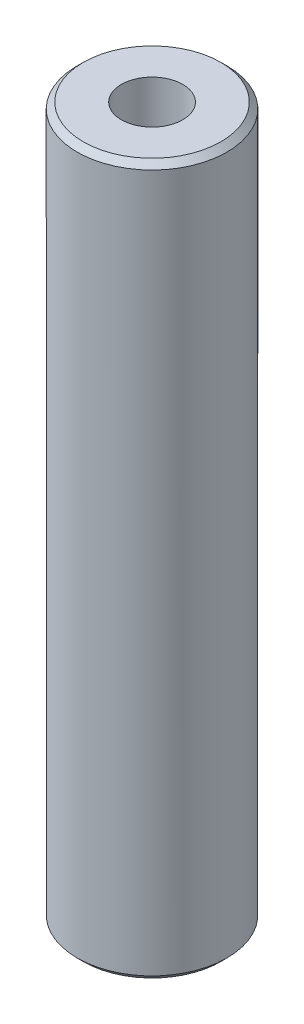
SolidWorks part; units mm, degrees
ref_plane "Front Plane" through (0, 0, 0) normal (0, 0, 1) x (1, 0, 0)
ref_plane "Top Plane" through (0, 0, 0) normal (0, 1, 0) x (1, 0, 0)
ref_plane "Right Plane" through (0, 0, 0) normal (1, 0, 0) x (0, 0, -1)
sketch "Sketch1" plane through (0, 0, 0) normal (0, 1, 0) x (1, 0, 0)
  circle A0 centre (0, 0) radius 52.5
  dimension "SHAFT_OD" = 105
extrude "Boss-Extrude1" add sketch "Sketch1" along normal blind 498.0194
sketch "Sketch2" plane through (0, 0, 0) normal (0, 1, 0) x (1, 0, 0)
  circle A0 centre (0, 0) radius 21.5321
  dimension "BORE_D" = 43.0642
extrude "Cut-Extrude1" cut sketch "Sketch2" along normal through all
chamfer "Chamfer1" distance 4.1875 angle 45.27 2 edges at (0, 498.0194, 52.5) (0, 0, 52.5) first distance on face at (0, 498.0194, 52.5) first distance on face at (0, 0, 21.5321)
